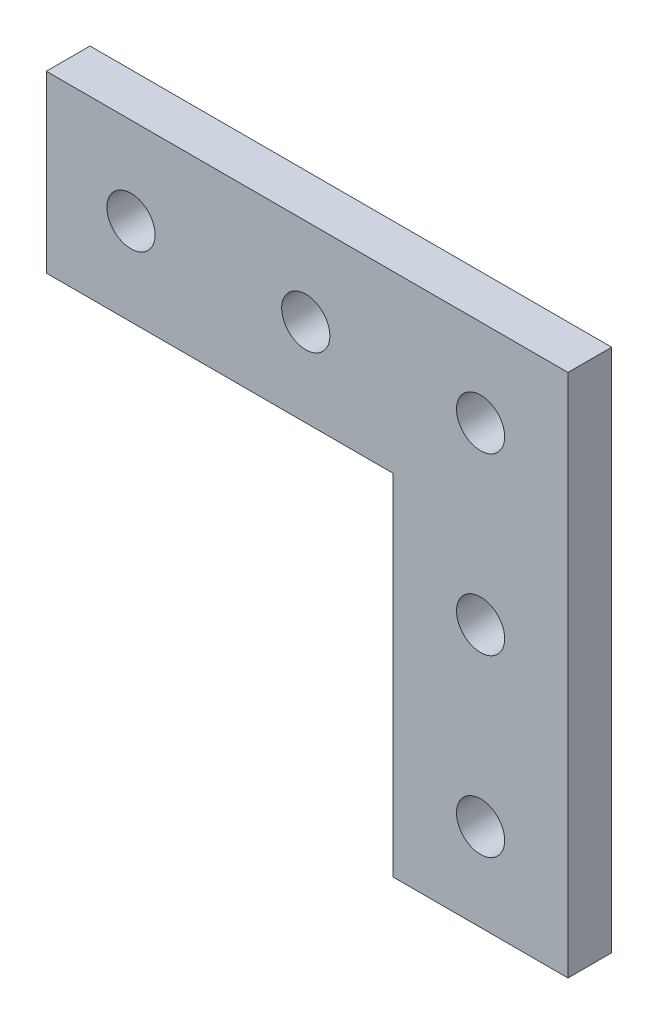
SolidWorks part; units mm, degrees
ref_plane "Front Plane" through (0, 0, 0) normal (0, 0, 1) x (1, 0, 0)
ref_plane "Top Plane" through (0, 0, 0) normal (0, 1, 0) x (1, 0, 0)
ref_plane "Right Plane" through (0, 0, 0) normal (1, 0, 0) x (0, 0, -1)
sketch "Sketch1" plane through (0, 0, 0) normal (0, 0, 1) x (1, 0, 0)
  line L0 (12.7, 0) -> (-12.7, 0)
  line L1 (-12.7, 0) -> (-12.7, 50.8)
  line L7 (12.7, 50.8) -> (12.7, 0)
  line L8 (12.7, 50.8) -> (12.7, 76.2)
  line L10 (-63.1, 76.2) -> (-63.1, 50.8)
  line L12 (12.7, 76.2) -> (-63.1, 76.2)
  line L13 (-63.1, 50.8) -> (-12.7, 50.8)
  dimension "D1" = 25.4
  dimension "D2" = 12.7
  dimension "D3" = 50.8
  dimension "D4" = 50.4
  dimension "D5" = 25.4
extrude "Boss-Extrude1" add sketch "Sketch1" along normal blind 6.35
sketch "Sketch2" plane through (0, 0, 6.35) normal (0, 0, 1) x (1, 0, 0)
  line L0 (0, 0) -> (0, 67) construction
  line L2 (-28.9, 63.5) -> (-21.9, 63.5) construction
  line L5 (-12.7, 0) -> (12.7, 0) construction
  line L6 (-3.5, 63.5) -> (3.5, 63.5) construction
  line L7 (0, 63.5) -> (-63.1, 63.5) construction
  line L8 (-63.1, 76.2) -> (-63.1, 50.8) construction
  circle A0 centre (0, 63.5) radius 3.5
  circle A2 centre (-25.4, 63.5) radius 3.5
  circle A3 centre (0, 38.1) radius 3.5
  circle A4 centre (0, 12.7) radius 3.5
  circle A5 centre (-50.8, 63.5) radius 3.5
  point P24 (0, 0)
  dimension "D1" = 7
  dimension "D2" = 7
  dimension "D3" = 7
  dimension "D4" = 7
  dimension "D5" = 7
  dimension "D6" = 12.7
  dimension "D7" = 25.4
  dimension "D8" = 25.4
  dimension "D9" = 25.4
extrude "Cut-Extrude1" cut sketch "Sketch2" against normal through all
